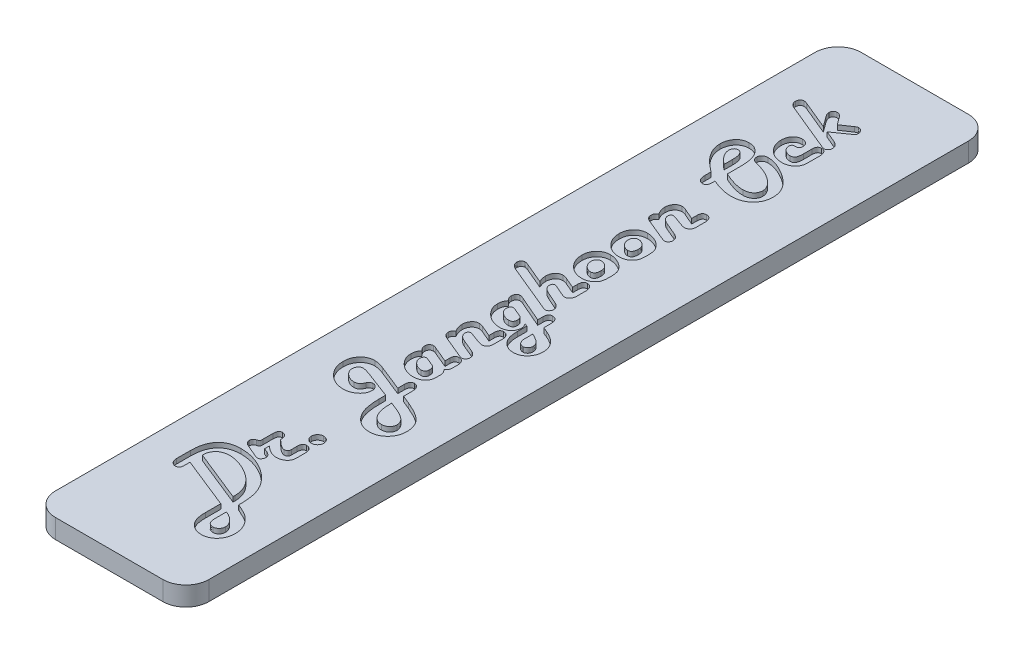
SolidWorks part; units mm, degrees
ref_plane "Front Plane" through (0, 0, 0) normal (0, 0, 1) x (1, 0, 0)
ref_plane "Top Plane" through (0, 0, 0) normal (0, 1, 0) x (1, 0, 0)
ref_plane "Right Plane" through (0, 0, 0) normal (1, 0, 0) x (0, 0, -1)
sketch "Sketch1" plane through (0, 0, 0) normal (0, 0, 1) x (1, 0, 0)
  line L0 (0, 1.5875) -> (0, -1.5875)
  line L1 (-12.7, 0) -> (12.7, 0) construction
  point P6 (0, 0)
  dimension "Width" = 25.4
  dimension "Thk" = 3.175
sketch "Sketch2" plane through (0, 0, 0) normal (1, 0, 0) x (0, 0, -1)
  line L0 (66.675, 0) -> (-66.675, 0)
  point P4 (0, 0)
  dimension "Length" = 133.35
sketch "Sketch3" plane through (0, 0, 0) normal (0, 0, 1) x (1, 0, 0)
  line L1 (12.7, 1.5875) -> (-12.7, 1.5875)
  line L2 (12.7, 1.5875) -> (12.7, -1.5875)
  line L3 (12.7, -1.5875) -> (-12.7, -1.5875)
  line L4 (-12.7, 1.5875) -> (-12.7, -1.5875)
  line L5 (12.7, 1.5875) -> (-12.7, -1.5875) construction
  line L6 (12.7, -1.5875) -> (-12.7, 1.5875) construction
  point P0 (0, 0)
extrude "Boss-Extrude1" add sketch "Sketch3" along normal up to vertex (66.675 mm away) and the other way up to vertex (66.675 mm away) up to point (0, 0, 66.675) other way up to point (0, 0, -66.675)
sketch "Sketch5" plane through (0, 1.5875, 0) normal (0, 1, 0) x (1, 0, 0)
  line L0 (-9.398, 66.929) -> (9.652, 66.929) construction
  line L1 (12.954, 63.627) -> (12.954, -63.373) construction
  line L2 (9.652, -66.675) -> (-9.398, -66.675) construction
  line L3 (-12.7, -63.373) -> (-12.7, 63.627) construction
  line L12 (12.7, -66.675) -> (12.7, 66.675)
  line L13 (12.7, 66.675) -> (-12.7, 66.675)
  line L14 (-12.7, 66.675) -> (-12.7, -66.675)
  line L15 (-12.7, -66.675) -> (12.7, -66.675)
  line L16 (12.7, -62.865) -> (12.7, 62.865)
  line L17 (8.89, 66.675) -> (-8.89, 66.675)
  line L18 (-12.7, 62.865) -> (-12.7, -62.865)
  line L19 (-8.89, -66.675) -> (8.89, -66.675)
  arc A0 (9.652, -66.675) -> (12.954, -63.373) centre (9.652, -63.373) ccw construction
  arc A1 (9.652, -66.675) -> (12.954, -63.373) centre (9.652, -63.373) ccw construction
  arc A2 (-12.7, -63.373) -> (-9.398, -66.675) centre (-9.398, -63.373) ccw construction
  arc A3 (-12.7, -63.373) -> (-9.398, -66.675) centre (-9.398, -63.373) ccw construction
  arc A4 (12.954, 63.627) -> (9.652, 66.929) centre (9.652, 63.627) ccw construction
  arc A5 (12.954, 63.627) -> (9.652, 66.929) centre (9.652, 63.627) ccw construction
  arc A6 (-9.398, 66.929) -> (-12.7, 63.627) centre (-9.398, 63.627) ccw construction
  arc A7 (-9.398, 66.929) -> (-12.7, 63.627) centre (-9.398, 63.627) ccw construction
  arc A8 (12.7, 62.865) -> (8.89, 66.675) centre (8.89, 62.865) ccw
  arc A9 (-8.89, 66.675) -> (-12.7, 62.865) centre (-8.89, 62.865) ccw
  arc A10 (12.7, -62.865) -> (8.89, -66.675) centre (8.89, -62.865) cw
  arc A11 (-8.89, -66.675) -> (-12.7, -62.865) centre (-8.89, -62.865) cw
  dimension "D2" = 3.81
  dimension "D1" = 0
extrude "Cut-Extrude2" cut sketch "Sketch5" against normal through all flip side to cut
sketch "Sketch4" plane through (0, 1.5875, 0) normal (0, 1, 0) x (1, 0, 0)
  line L0 (0, 0) -> (2.54, 0) construction
  line L1 (2.54, -66.675) -> (2.54, 66.675) construction
  line L2 (8.89, 66.675) -> (-8.89, 66.675) construction
  text T0 "Dr. Janghoon Ock" font "Harlow Solid Italic" height 10
  point P8 (2.54, 0)
  dimension "D1" = 2.54
extrude "Cut-Extrude1" cut sketch "Sketch4" against normal blind 0.7937
